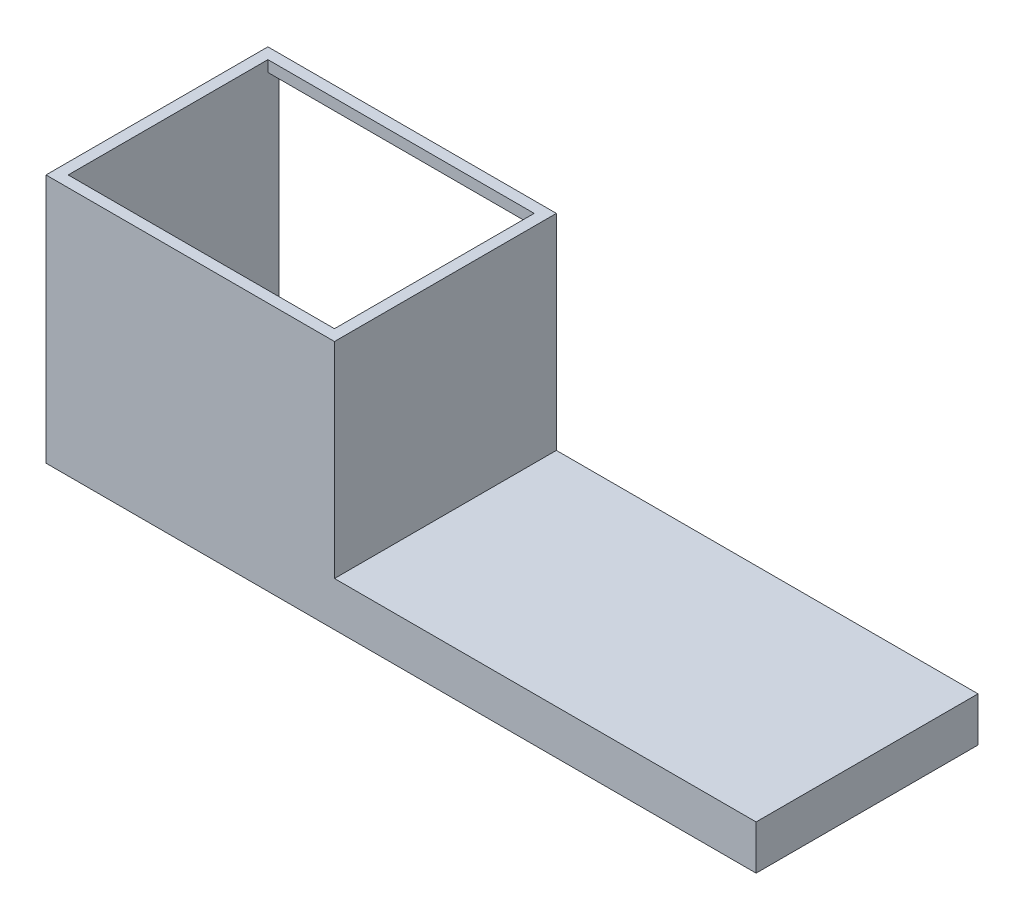
SolidWorks part; units mm, degrees
ref_plane "Front Plane" through (0, 0, 0) normal (0, 0, 1) x (1, 0, 0)
ref_plane "Top Plane" through (0, 0, 0) normal (0, 1, 0) x (1, 0, 0)
ref_plane "Right Plane" through (0, 0, 0) normal (1, 0, 0) x (0, 0, -1)
sketch "Sketch1" plane through (0, 0, 0) normal (0, 0, 1) x (1, 0, 0)
  line L1 (32, -11.25) -> (-32, -11.25)
  line L2 (32, -11.25) -> (32, 11.25)
  line L3 (32, 11.25) -> (-32, 11.25)
  line L4 (-32, -11.25) -> (-32, 11.25)
  line L5 (32, -11.25) -> (-32, 11.25) construction
  line L6 (32, 11.25) -> (-32, -11.25) construction
  point P0 (0, 0)
  dimension "D1" = 64
  dimension "D2" = 22.5
extrude "body" add sketch "Sketch1" along normal blind 20
sketch "Sketch2" plane through (0, 0, 20) normal (0, 0, 1) x (1, 0, 0)
  line L1 (32, 11.25) -> (-6, 11.25)
  line L2 (32, 11.25) -> (32, -7.25)
  line L3 (32, -7.25) -> (-6, -7.25)
  line L4 (-6, 11.25) -> (-6, -7.25)
  dimension "D1" = 38
  dimension "D2" = 18.5
extrude "remove_material" cut sketch "Sketch2" against normal through all
sketch "Sketch3" plane through (0, 0, 0) normal (0, 0, -1) x (-1, 0, 0)
  line L0 (31, -10.25) -> (-31, -10.25)
  line L1 (-31, -10.25) -> (-31, -8.25)
  line L2 (-31, -8.25) -> (7, -8.25)
  line L3 (7, -8.25) -> (7, 10.25)
  line L4 (7, 10.25) -> (31, 10.25)
  line L5 (31, 10.25) -> (31, -10.25)
  line L6 (32, -11.25) -> (-32, -11.25) construction
  line L7 (32, 11.25) -> (32, -11.25) construction
  line L8 (6, 11.25) -> (32, 11.25) construction
  line L9 (6, 11.25) -> (6, -7.25) construction
  line L10 (6, -7.25) -> (-32, -7.25) construction
  line L11 (-32, -11.25) -> (-32, -7.25) construction
  dimension "D1" = 1
  dimension "D2" = 1
  dimension "D3" = 1
  dimension "D4" = 1
  dimension "D5" = 1
  dimension "D6" = 1
extrude "ducting" cut sketch "Sketch3" against normal blind 19
sketch "Sketch4" plane through (0, 11.25, 0) normal (0, 1, 0) x (1, 0, 0)
  line L0 (-6, -10) -> (-32, -10) construction
  line L1 (-6, 0) -> (-6, -20) construction
  line L2 (-32, -20) -> (-32, 0) construction
  line L4 (-6, -20) -> (-32, -20) construction
  line L5 (-19, -20) -> (-19, 0) construction
  line L6 (-6, 0) -> (-32, 0) construction
  line L7 (-31, -1) -> (-7, -1)
  line L8 (-31, -1) -> (-31, -19)
  line L9 (-31, -19) -> (-7, -19)
  line L10 (-7, -1) -> (-7, -19)
  line L11 (-31, -1) -> (-7, -19) construction
  line L12 (-31, -19) -> (-7, -1) construction
  point P6 (-19, -10)
  dimension "D1" = 1
  dimension "D2" = 1
extrude "inlet" cut sketch "Sketch4" against normal blind 1
sketch "Sketch5" plane through (0, -11.25, 0) normal (0, -1, 0) x (1, 0, 0)
  line L0 (32, 20) -> (32, 0) construction
  line L1 (31, 1) -> (-21, 1)
  line L2 (31, 1) -> (31, 19)
  line L3 (31, 19) -> (-21, 19)
  line L4 (-21, 1) -> (-21, 19)
  line L5 (-32, 0) -> (32, 0) construction
  line L6 (-32, 20) -> (32, 20) construction
  dimension "D1" = 1
  dimension "D2" = 1
  dimension "D3" = 52
  dimension "D4" = 1
extrude "outlet" cut sketch "Sketch5" against normal blind 1
